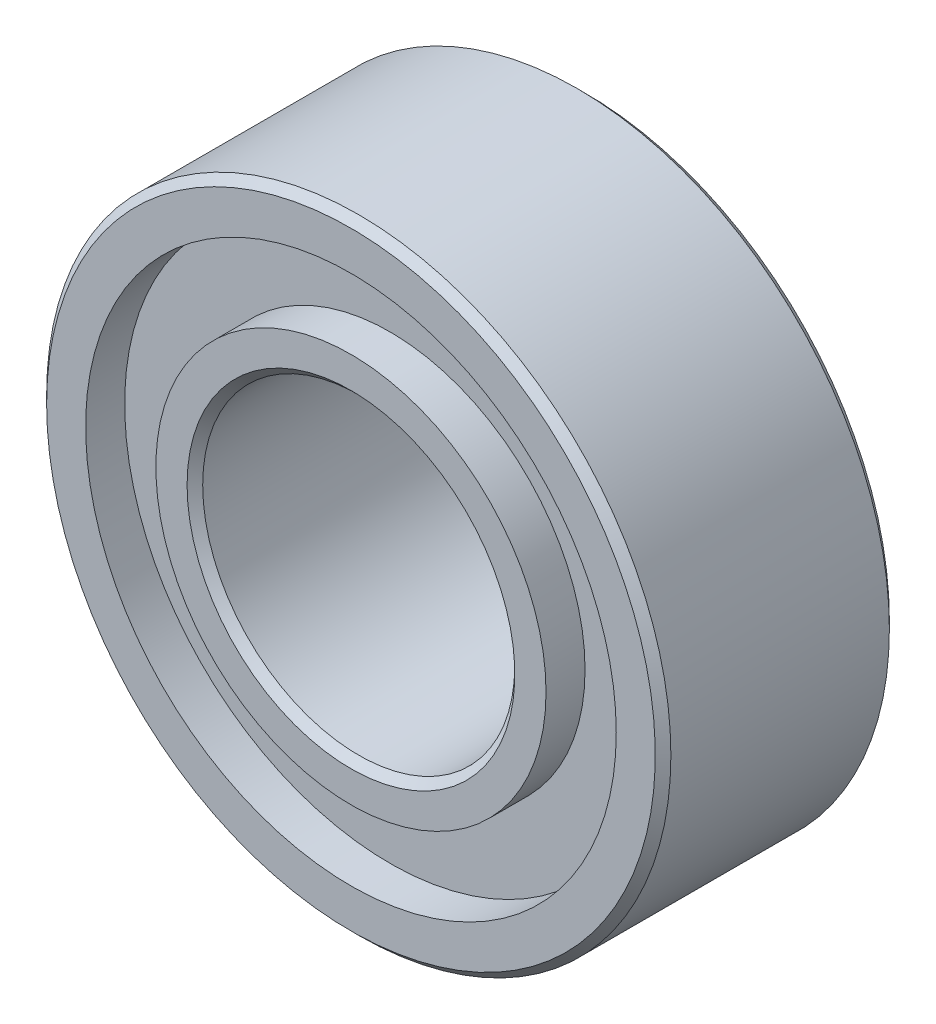
SolidWorks part; units mm, degrees
ref_plane "Ebene vorne" through (0, 0, 0) normal (0, 0, 1) x (1, 0, 0)
ref_plane "Ebene oben" through (0, 0, 0) normal (0, 1, 0) x (1, 0, 0)
ref_plane "Ebene rechts" through (0, 0, 0) normal (1, 0, 0) x (0, 0, -1)
sketch "Skizze2" plane through (0, 0, 0) normal (1, 0, 0) x (0, 0, -1)
  line L0 (-11.8458, 0) -> (13.4965, 0) construction
  line L1 (0, 16.288) -> (0, -14.1034) construction
  line L2 (-1.5, 2) -> (1.5, 2)
  line L3 (1.5, 2) -> (1.5, 2.5)
  line L4 (1.5, 2.5) -> (1, 2.5)
  line L5 (1, 2.5) -> (1, 3.4)
  line L6 (1, 3.4) -> (1.5, 3.4)
  line L7 (1.5, 3.4) -> (1.5, 4)
  line L8 (1.5, 4) -> (-1.5, 4)
  line L9 (-1.5, 3.4) -> (-1.5, 4)
  line L10 (-1, 3.4) -> (-1.5, 3.4)
  line L11 (-1, 2.5) -> (-1, 3.4)
  line L12 (-1.5, 2.5) -> (-1, 2.5)
  line L13 (-1.5, 2) -> (-1.5, 2.5)
  point P5 (0, 4)
  point P19 (0, 2)
  dimension "D1" = 4
  dimension "D2" = 8
  dimension "D3" = 3
  dimension "D4" = 5
  dimension "D5" = 6.8
  dimension "D6" = 2
revolve "Rotation1" add sketch "Skizze2" angle 360 about L0
ref_axis "Achse1" through (0, 0, -1.65) along (0, 0, 1)
chamfer "Fase1" distance 0.1 angle 45 4 edges at (2, 0, -1.5) (2, 0, 1.5) (4, 0, -1.5) (4, 0, 1.5)
